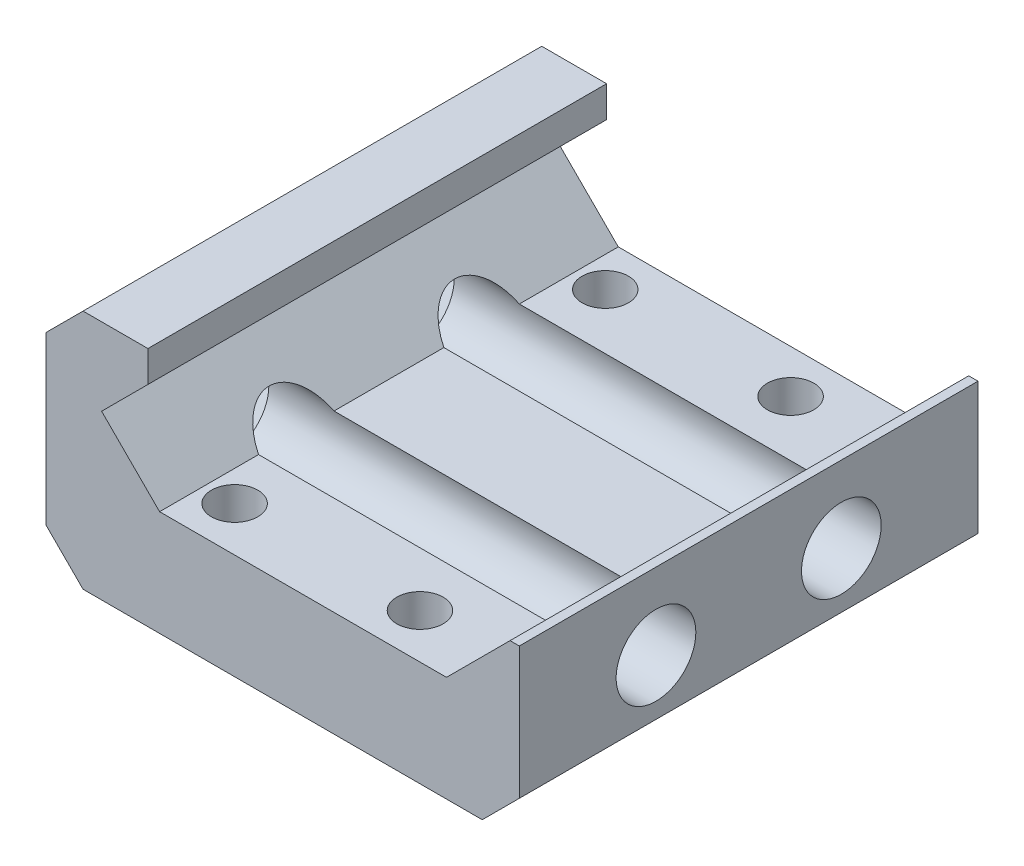
SolidWorks part; units mm, degrees
ref_plane "Płaszczyzna przednia" through (0, 0, 0) normal (0, 0, 1) x (1, 0, 0)
ref_plane "Płaszczyzna górna" through (0, 0, 0) normal (0, 1, 0) x (1, 0, 0)
ref_plane "Płaszczyzna prawa" through (0, 0, 0) normal (1, 0, 0) x (0, 0, -1)
sketch "Szkic1" plane through (0, 0, 0) normal (0, 0, 1) x (1, 0, 0)
  line L0 (-3, 4.18) -> (2.5, 4.18)
  line L2 (-3, -8.82) -> (-3, 4.18)
  line L5 (22.74, -1) -> (22.74, -7.02) construction
  line L6 (1.37, -1.37) -> (20.37, -1.37) construction
  line L7 (2.5, 4.18) -> (2.5, 2.5)
  line L8 (2.5, 2.5) -> (0, 0)
  line L9 (0, 0) -> (3.13, -3.13)
  line L10 (3.13, -3.13) -> (18.61, -3.13)
  line L11 (18.61, -3.13) -> (22.54, 0.8)
  line L14 (22.54, 0.8) -> (22.54, -6.82)
  line L17 (22.54, -6.82) -> (20.54, -8.82)
  line L18 (-3, -8.82) -> (20.54, -8.82)
  line L19 (1.37, -1.37) -> (1.37, 1.37) construction
  line L20 (1.37, 1.37) -> (20.37, 1.37) construction
  line L21 (20.37, -1.37) -> (20.37, 1.37) construction
  dimension "D1" = 45
  dimension "D2" = 45
  dimension "D3" = 5.5
  dimension "D4" = 1.68
  dimension "D5" = 13
  dimension "D6" = 2
  dimension "D7" = 19
  dimension "D8" = 2.74
  dimension "D9" = 4.5
  dimension "D10" = 3
  dimension "D11" = 0.2
extrude "Dodanie-wyciągnięcie3" add sketch "Szkic1" along normal blind 24.75
sketch "Szkic3" plane through (22.54, 0, 0) normal (1, 0, 0) x (0, 0, -1)
  line L1 (-7.375, -3.82) -> (-17.375, -3.82) construction
  line L2 (-24.75, 0) -> (0, 0) construction
  line L3 (-24.75, -6.82) -> (0, -6.82) construction
  line L4 (-24.75, -6.82) -> (0, -6.82) construction
  line L5 (-12.375, -6.82) -> (-12.375, -3.82) construction
  circle A0 centre (-17.375, -3.82) radius 2.15
  circle A1 centre (-7.375, -3.82) radius 2.15
  dimension "D1" = 10
  dimension "D2" = 4.3
  dimension "D3" = 3.82
extrude "Wytnij-wyciągnięcie1" cut sketch "Szkic3" against normal through all
sketch "Szkic4" plane through (0, -3.13, 0) normal (0, 1, 0) x (1, 0, 0)
  line L0 (18.61, -24.75) -> (3.13, -24.75) construction
  circle A0 centre (0, -2.75) radius 2
  circle A1 centre (0, -22) radius 2
  dimension "D2" = 2.75
  dimension "D3" = 2.75
extrude "Wytnij-wyciągnięcie2" [suppressed] cut sketch "Szkic4" against normal blind 6
sketch "Szkic7" [suppressed] plane through (0, -3.13, 0) normal (0, 1, 0) x (1, 0, 0)
  circle A0 centre (0, -2.75) radius 2.5
  circle A1 centre (0, -22) radius 2.5
  dimension "D1" = 2.75
  dimension "D2" = 19.25
extrude "Wytnij-wyciągnięcie3" [suppressed] cut sketch "Szkic7" against normal blind 1.5
sketch "Sketch1" plane through (0, 0, 24.75) normal (0, 0, 1) x (1, 0, 0)
  line L0 (22.04, 0.3) -> (22.54, 0.3)
  line L1 (22.54, 0.8) -> (18.61, -3.13) construction
  line L2 (22.54, -6.82) -> (22.54, 0.8) construction
  line L13 (-3, -8.82) -> (20.54, -8.82)
  line L14 (20.54, -8.82) -> (22.54, -6.82)
  line L15 (22.54, -6.82) -> (22.54, 0.8)
  line L16 (22.54, 0.8) -> (18.61, -3.13)
  line L17 (18.61, -3.13) -> (3.13, -3.13)
  line L18 (3.13, -3.13) -> (0, 0)
  line L19 (0, 0) -> (2.5, 2.5)
  line L20 (2.5, 2.5) -> (2.5, 4.18)
  line L21 (2.5, 4.18) -> (-3, 4.18)
  line L22 (-3, 4.18) -> (-3, -8.82)
  line L25 (22.54, 0.3) -> (22.54, 0.8)
  line L26 (22.54, 0.8) -> (22.04, 0.3)
  dimension "D1" = 0.5
  dimension "D2" = 0
extrude "Cut-Extrude1" cut sketch "Sketch1" against normal through all
sketch "Sketch3" plane through (22.54, 0, 0) normal (1, 0, 0) x (0, 0, -1)
  circle A0 centre (-17.375, -3.82) radius 2.65
  circle A1 centre (-7.375, -3.82) radius 2.65
  dimension "D1" = 5.3
chamfer "Chamfer1" distance 2 angle 45 2 edges at (-3, 4.18, 12.375) (-3, -8.82, 12.375)
hole_wizard "Ø2.5 (2.5) Diameter Hole1" positions "Sketch4" profile "Sketch5" hole size "Ø2.5" standard "DIN" end condition through all
sketch "Sketch4" plane through (0, -8.82, 0) normal (0, -1, 0) x (-1, 0, 0)
  line L0 (-9.77, -19.9336) -> (-9.77, -24.75) construction
  line L4 (-4.77, -22.3418) -> (-9.77, -22.3418) construction
  line L6 (-9.77, 0) -> (-9.77, -4.8164) construction
  line L10 (-9.32, -2.3418) -> (-4.77, -2.3418) construction
  line L14 (1, -24.75) -> (-20.54, -24.75) construction
  point P0 (-4.77, -2.3418)
  point P4 (-14.77, -2.3418)
  point P5 (-14.77, -22.3418)
  point P6 (-4.77, -22.3418)
  dimension "D3" = 10
  dimension "D4" = 20
  dimension "D5" = 5
  dimension "D1" = 2
  dimension "D2" = 2
sketch "Sketch5" plane through (4.77, -8.82, 2.3418) normal (1, 0, 0) x (0, 0, -1)
  line L0 (0, 0) -> (0, 13)
  line L1 (0, 13) -> (1.25, 13)
  line L2 (1.25, 13) -> (1.25, 0)
  line L5 (1.25, 0) -> (0, 0)
  line L11 (0, -6.35) -> (0, 107.95) construction
  dimension "Thru Hole Dia." = 2.5
  dimension "Thru Hole Depth" = 13
sketch "Sketch6" plane through (-3, 0, 0) normal (-1, 0, 0) x (0, 0, 1)
  line L1 (9.3669, -7.27) -> (11.3587, -3.82)
  line L2 (11.3587, -3.82) -> (9.3669, -0.37)
  line L3 (9.3669, -0.37) -> (5.3831, -0.37)
  line L4 (5.3831, -0.37) -> (3.3913, -3.82)
  line L5 (3.3913, -3.82) -> (5.3831, -7.27)
  line L6 (5.3831, -7.27) -> (9.3669, -7.27)
  line L7 (15.3831, -7.27) -> (19.3669, -7.27)
  line L8 (19.3669, -7.27) -> (21.3587, -3.82)
  line L9 (21.3587, -3.82) -> (19.3669, -0.37)
  line L10 (19.3669, -0.37) -> (15.3831, -0.37)
  line L11 (15.3831, -0.37) -> (13.3913, -3.82)
  line L12 (13.3913, -3.82) -> (15.3831, -7.27)
  circle A0 centre (7.375, -3.82) radius 3.45 construction
  circle A1 centre (17.375, -3.82) radius 3.45 construction
  dimension "D1" = 6.9
extrude "Cut-Extrude2" cut sketch "Sketch6" against normal blind 2.5
